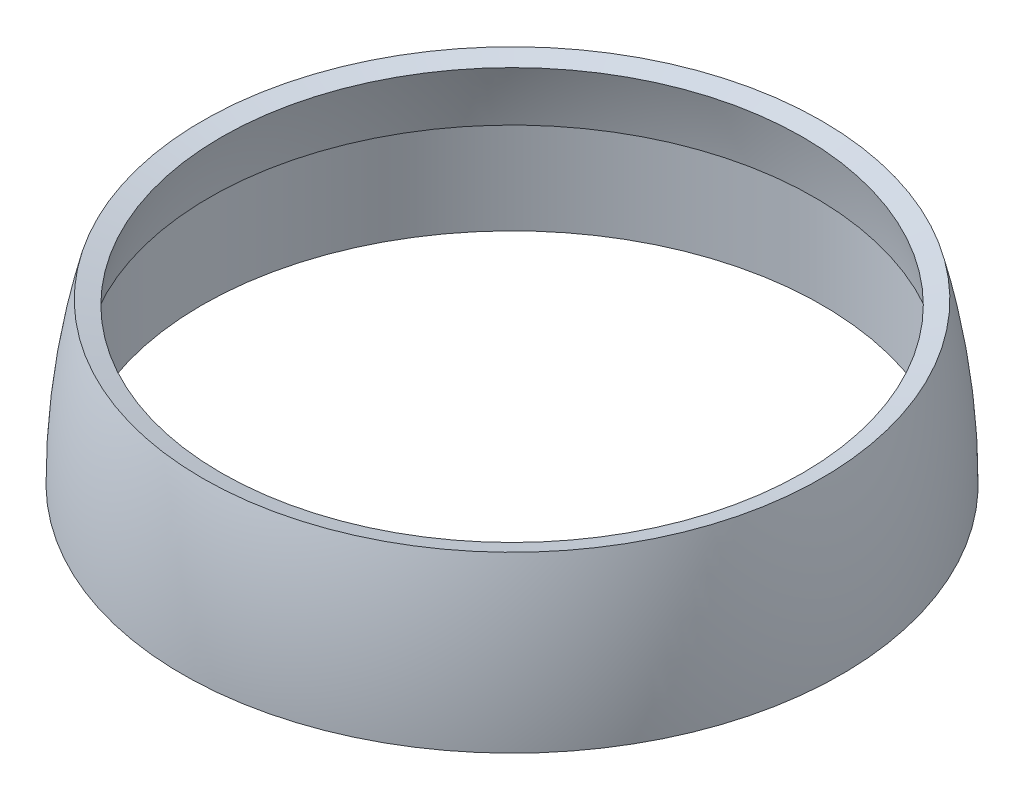
SolidWorks part; units mm, degrees
ref_plane "Front Plane" through (0, 0, 0) normal (0, 0, 1) x (1, 0, 0)
ref_plane "Top Plane" through (0, 0, 0) normal (0, 1, 0) x (1, 0, 0)
ref_plane "Right Plane" through (0, 0, 0) normal (1, 0, 0) x (0, 0, -1)
sketch "Sketch1" plane through (0, 0, 0) normal (0, 1, 0) x (1, 0, 0)
  circle A0 centre (0, 0) radius 16
  dimension "D1" = 32
sketch "Sketch2" plane through (0, 0, 0) normal (0, 0, 1) x (1, 0, 0)
  line L0 (15, 8) -> (-8.4558, 8) construction
  line L8 (0, 0) -> (0, 23.5897) construction
  line L13 (0, 0) -> (16, 0) construction
  line L14 (16, 0) -> (16, -6.6635) construction
  arc A0 (15, 8) -> (16, 0) centre (-16.5, 0) cw
  dimension "D1" = 8
  dimension "D2" = 1
revolve "Revolve-Thin1" add sketch "Sketch2" angle 360 about L8 wall 1
sketch "Sketch3" plane through (0, 0, 0) normal (0, 0, 1) x (1, 0, 0)
  line L0 (16, 0) -> (16, 5)
  line L1 (-17, 0) -> (17, 0) construction
  line L2 (16, 5) -> (0, 5)
  line L3 (0, 5) -> (0, 0) construction
  line L4 (0, 0) -> (16, 0)
  line L5 (-16, 0) -> (16, 0) construction
  line L6 (0, 5) -> (0, 0)
  arc A0 (16, 0) -> (15, 8) centre (-16.5, 0) ccw construction
  dimension "D1" = 5
revolve "Cut-Revolve1" cut sketch "Sketch3" angle 360 about L3
